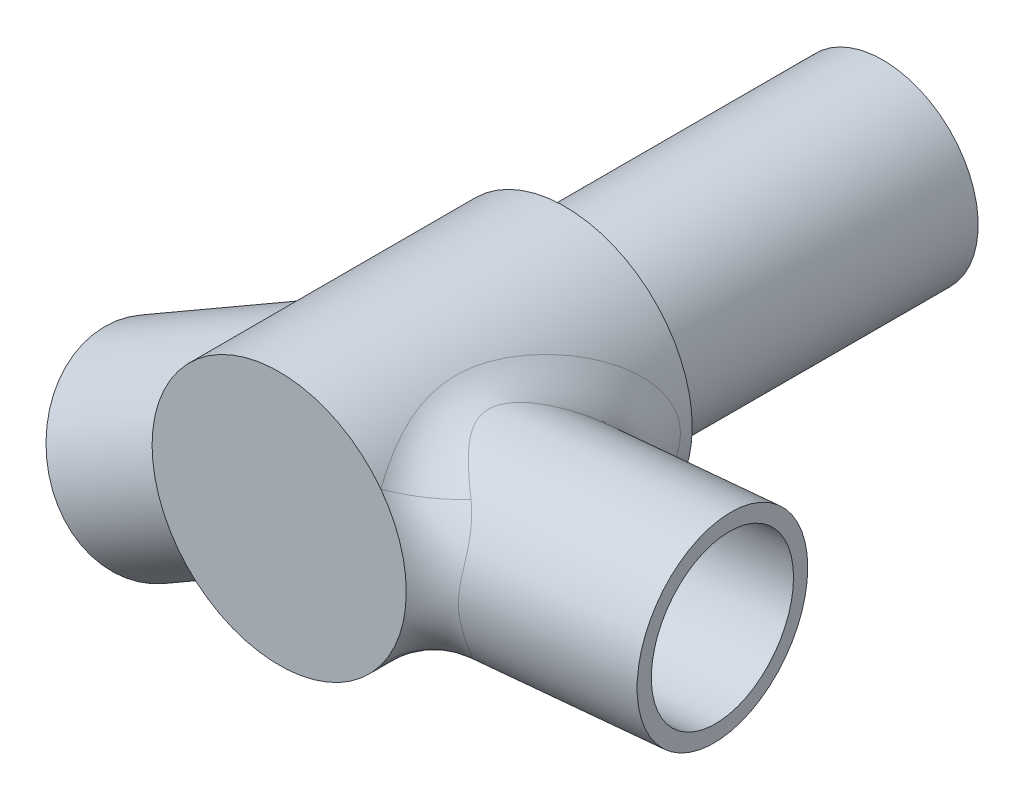
SolidWorks part; units mm, degrees
ref_plane "Alzado" through (0, 0, 0) normal (0, 0, 1) x (1, 0, 0)
ref_plane "Planta" through (0, 0, 0) normal (0, 1, 0) x (1, 0, 0)
ref_plane "Vista lateral" through (0, 0, 0) normal (1, 0, 0) x (0, 0, -1)
sketch "Croquis1" plane through (0, 0, 0) normal (0, 0, 1) x (1, 0, 0)
  circle A0 centre (0, 0) radius 15
  dimension "D1" = 30
extrude "Saliente-Extruir1" add sketch "Croquis1" along normal mid plane 70
sketch "Croquis2" plane through (0, 0, 0) normal (0, 0, 1) x (1, 0, 0)
  line L0 (0, 0) -> (-23.6151, 0) construction
  line L1 (0, 0) -> (-50, -28.8675) construction
  line L2 (0, 0) -> (57.735, 0) construction
  dimension "D1" = 50
  dimension "D2" = 30
sketch3d "Croquis3D1"
  line L0 (0, 0, 35) -> (0, 0, -35) construction
  line L2 (0, 0, 35) -> (0, 0, -35) construction
  line L3 (-45.8993, -26.5, 0) -> (-45.8993, -26.5, 9.0252) construction
  line L4 (0, 0, 0) -> (-50, -28.8675, 0) construction
  line L5 (-45.8993, -26.5, 9.0252) -> (0, 0, 9.0252) construction
  line L6 (49.7502, 0, 0) -> (49.7502, 0, 15) construction
  line L7 (0, 0, 0) -> (57.735, 0, 0) construction
  line L8 (49.7502, 0, 15) -> (0, 0, 19.992) construction
  point P4 (0, 0, 0)
  dimension "D1" = 50
  dimension "D3" = 84.27
  dimension "D2" = 15
  dimension "D4" = 53
ref_plane "Plano1" through (-45.8993, -26.5, 9.0252) normal (0.866, 0.5, 0) x (0, 0, -1)
sketch "Croquis3" plane through (-45.8993, -26.5, 9.0252) normal (0.866, 0.5, 0) x (0, 0, -1)
  circle A0 centre (0, 0) radius 15
  circle A1 centre (0, 0) radius 12.5
  dimension "D1" = 30
  dimension "D2" = 25
extrude "Saliente-Extruir2" add sketch "Croquis3" along normal up to surface (53 mm away) up to face at (15, 0, 35)
ref_plane "Plano2" through (49.7502, 0, 15) normal (0.995, 0, -0.0998) x (-0.0998, 0, -0.995)
sketch "Croquis4" plane through (49.7502, 0, 15) normal (0.995, 0, -0.0998) x (-0.0998, 0, -0.995)
  circle A0 centre (0, 0) radius 12.5
  circle A1 centre (0, 0) radius 15
  dimension "D1" = 30
  dimension "D2" = 25
extrude "Saliente-Extruir3" add sketch "Croquis4" against normal up to surface (33.6704 mm away) up to face at (15, 0, -35)
sketch "Croquis6" plane through (0, 0, 35) normal (0, 0, 1) x (1, 0, 0)
  circle A0 centre (0, 0) radius 20
  dimension "D1" = 40
extrude "Saliente-Extruir5" add sketch "Croquis6" against normal blind 45
fillet "Redondeo1" radius 10 2 edges at (-18.958, 6.3713, 8.7105) (19.9192, 1.796, 32.9602)
sketch "Croquis8" plane through (0, 0, -35) normal (0, 0, -1) x (-1, 0, 0)
  circle A0 centre (0, 0) radius 15
extrude "Saliente-Extruir6" add sketch "Croquis8" along normal blind 25
